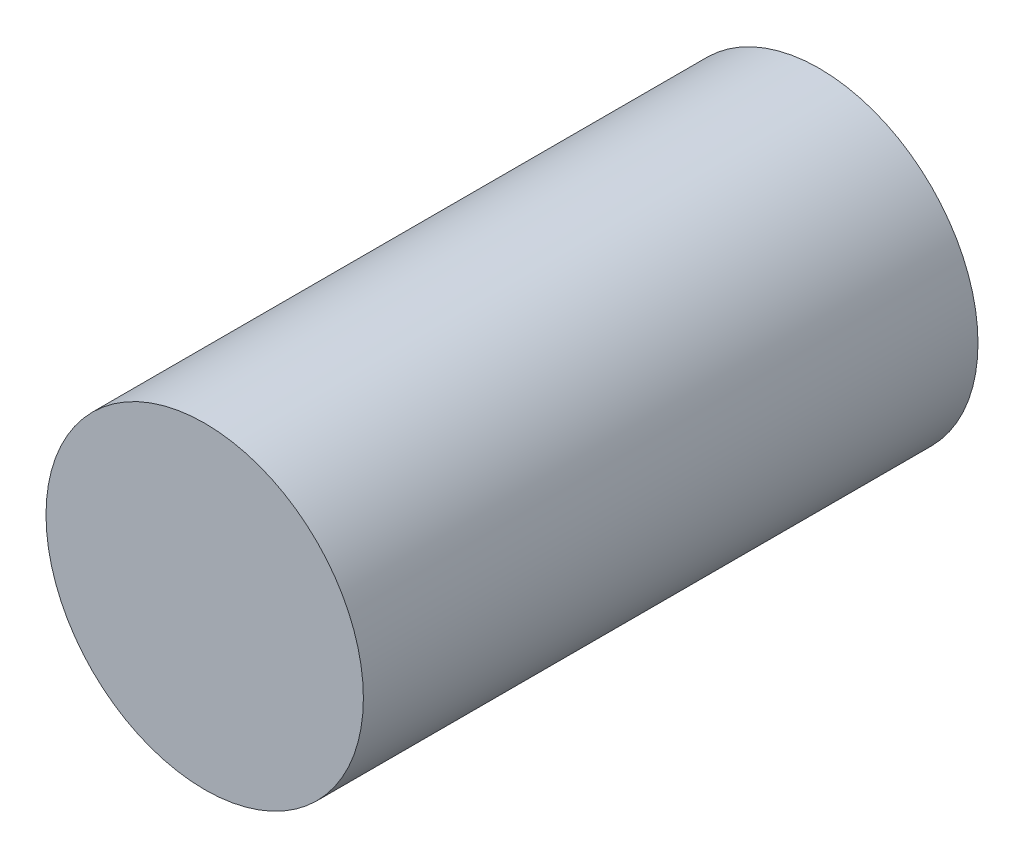
SolidWorks part; units mm, degrees
ref_plane "Front Plane" through (0, 0, 0) normal (0, 0, 1) x (1, 0, 0)
ref_plane "Top Plane" through (0, 0, 0) normal (0, 1, 0) x (1, 0, 0)
ref_plane "Right Plane" through (0, 0, 0) normal (1, 0, 0) x (0, 0, -1)
sketch "Sketch1" plane through (0, 0, 0) normal (0, 0, 1) x (1, 0, 0)
  circle A0 centre (0, 0) radius 30
  circle A1 centre (0, 0) radius 31.5
  dimension "D1" = 60
  dimension "D2" = 1.5
extrude "Boss-Extrude1" add sketch "Sketch1" along normal blind 120
sketch "Sketch2" plane through (0, 0, 120) normal (0, 0, 1) x (1, 0, 0)
  circle A1 centre (0, 0) radius 31.5
  circle A2 centre (0, 0) radius 31.5
  dimension "D1" = 0
extrude "Boss-Extrude2" add sketch "Sketch2" along normal blind 2
